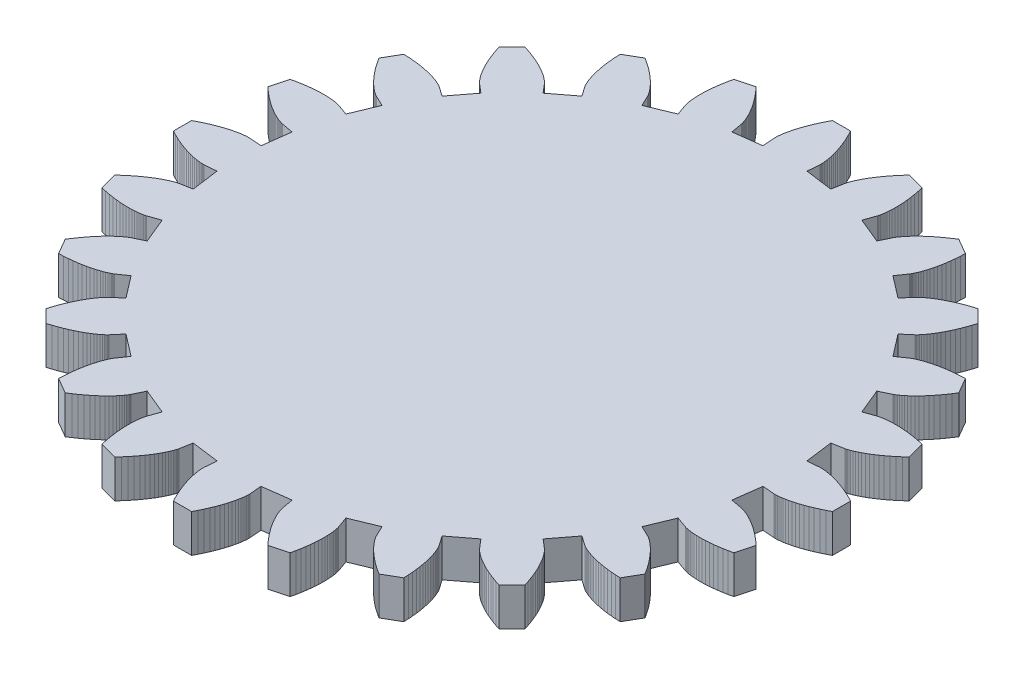
SolidWorks part; units mm, degrees
ref_plane "Front Plane" through (0, 0, 0) normal (0, 0, 1) x (1, 0, 0)
ref_plane "Top Plane" through (0, 0, 0) normal (0, 1, 0) x (1, 0, 0)
ref_plane "Right Plane" through (0, 0, 0) normal (1, 0, 0) x (0, 0, -1)
sketch "Sketch1" plane through (0, 0, 0) normal (0, 1, 0) x (1, 0, 0)
  line L0 (21.5303, 1.7338) -> (22.4799, 1.8102)
  line L1 (22.4799, 1.8102) -> (22.4901, 1.8109)
  line L2 (22.4901, 1.8109) -> (22.5209, 1.8119)
  line L3 (22.5209, 1.8119) -> (22.5723, 1.8121)
  line L4 (22.5723, 1.8121) -> (22.6443, 1.8102)
  line L5 (22.6443, 1.8102) -> (22.7366, 1.805)
  line L6 (22.7366, 1.805) -> (22.8493, 1.7953)
  line L7 (22.8493, 1.7953) -> (22.982, 1.7798)
  line L8 (22.982, 1.7798) -> (23.1345, 1.7573)
  line L9 (23.1345, 1.7573) -> (23.3066, 1.7266)
  line L10 (23.3066, 1.7266) -> (23.4977, 1.6865)
  line L11 (23.4977, 1.6865) -> (23.7075, 1.6359)
  line L12 (23.7075, 1.6359) -> (23.9356, 1.5735)
  line L13 (23.9356, 1.5735) -> (24.1813, 1.4982)
  line L14 (24.1813, 1.4982) -> (24.4441, 1.4089)
  line L15 (24.4441, 1.4089) -> (24.7233, 1.3046)
  line L16 (24.7233, 1.3046) -> (25.0183, 1.1841)
  line L17 (25.0183, 1.1841) -> (25.3283, 1.0464)
  line L18 (25.3283, 1.0464) -> (25.6525, 0.8905)
  line L19 (25.6525, 0.8905) -> (25.9901, 0.7155)
  line L20 (25.9901, 0.7155) -> (25.9901, -0.7155)
  line L21 (25.9901, -0.7155) -> (25.6525, -0.8905)
  line L22 (25.6525, -0.8905) -> (25.3283, -1.0464)
  line L23 (25.3283, -1.0464) -> (25.0183, -1.1841)
  line L24 (25.0183, -1.1841) -> (24.7233, -1.3046)
  line L25 (24.7233, -1.3046) -> (24.4441, -1.4089)
  line L26 (24.4441, -1.4089) -> (24.1813, -1.4982)
  line L27 (24.1813, -1.4982) -> (23.9356, -1.5735)
  line L28 (23.9356, -1.5735) -> (23.7075, -1.6359)
  line L29 (23.7075, -1.6359) -> (23.4977, -1.6865)
  line L30 (23.4977, -1.6865) -> (23.3066, -1.7266)
  line L31 (23.3066, -1.7266) -> (23.1345, -1.7573)
  line L32 (23.1345, -1.7573) -> (22.982, -1.7798)
  line L33 (22.982, -1.7798) -> (22.8493, -1.7953)
  line L34 (22.8493, -1.7953) -> (22.7366, -1.805)
  line L35 (22.7366, -1.805) -> (22.6443, -1.8102)
  line L36 (22.6443, -1.8102) -> (22.5723, -1.8121)
  line L37 (22.5723, -1.8121) -> (22.5209, -1.8119)
  line L38 (22.5209, -1.8119) -> (22.4901, -1.8109)
  line L39 (22.4901, -1.8109) -> (22.4799, -1.8102)
  line L40 (22.4799, -1.8102) -> (21.5303, -1.7338)
  line L41 (21.5303, -1.7338) -> (21.2454, -3.8977)
  line L42 (21.2454, -3.8977) -> (22.1824, -4.0696)
  line L43 (22.1824, -4.0696) -> (22.1925, -4.0717)
  line L44 (22.1925, -4.0717) -> (22.2225, -4.0787)
  line L45 (22.2225, -4.0787) -> (22.2722, -4.0918)
  line L46 (22.2722, -4.0918) -> (22.3412, -4.1122)
  line L47 (22.3412, -4.1122) -> (22.4291, -4.1411)
  line L48 (22.4291, -4.1411) -> (22.5354, -4.1797)
  line L49 (22.5354, -4.1797) -> (22.6595, -4.229)
  line L50 (22.6595, -4.229) -> (22.8011, -4.2902)
  line L51 (22.8011, -4.2902) -> (22.9593, -4.3644)
  line L52 (22.9593, -4.3644) -> (23.1335, -4.4526)
  line L53 (23.1335, -4.4526) -> (23.3231, -4.5558)
  line L54 (23.3231, -4.5558) -> (23.5272, -4.6751)
  line L55 (23.5272, -4.6751) -> (23.7451, -4.8114)
  line L56 (23.7451, -4.8114) -> (23.9758, -4.9657)
  line L57 (23.9758, -4.9657) -> (24.2185, -5.1387)
  line L58 (24.2185, -5.1387) -> (24.4723, -5.3314)
  line L59 (24.4723, -5.3314) -> (24.7361, -5.5447)
  line L60 (24.7361, -5.5447) -> (25.0089, -5.7792)
  line L61 (25.0089, -5.7792) -> (25.2897, -6.0357)
  line L62 (25.2897, -6.0357) -> (24.9194, -7.4178)
  line L63 (24.9194, -7.4178) -> (24.5479, -7.4995)
  line L64 (24.5479, -7.4995) -> (24.1944, -7.5662)
  line L65 (24.1944, -7.5662) -> (23.8593, -7.619)
  line L66 (23.8593, -7.619) -> (23.5432, -7.659)
  line L67 (23.5432, -7.659) -> (23.2465, -7.6875)
  line L68 (23.2465, -7.6875) -> (22.9695, -7.7057)
  line L69 (22.9695, -7.7057) -> (22.7127, -7.7148)
  line L70 (22.7127, -7.7148) -> (22.4763, -7.7161)
  line L71 (22.4763, -7.7161) -> (22.2605, -7.7107)
  line L72 (22.2605, -7.7107) -> (22.0655, -7.7)
  line L73 (22.0655, -7.7) -> (21.8914, -7.6851)
  line L74 (21.8914, -7.6851) -> (21.7383, -7.6673)
  line L75 (21.7383, -7.6673) -> (21.606, -7.648)
  line L76 (21.606, -7.648) -> (21.4947, -7.6282)
  line L77 (21.4947, -7.6282) -> (21.4042, -7.6093)
  line L78 (21.4042, -7.6093) -> (21.3342, -7.5925)
  line L79 (21.3342, -7.5925) -> (21.2846, -7.579)
  line L80 (21.2846, -7.579) -> (21.2551, -7.57)
  line L81 (21.2551, -7.57) -> (21.2453, -7.5668)
  line L82 (21.2453, -7.5668) -> (20.3479, -7.2472)
  line L83 (20.3479, -7.2472) -> (19.5127, -9.2637)
  line L84 (19.5127, -9.2637) -> (20.3732, -9.6722)
  line L85 (20.3732, -9.6722) -> (20.3824, -9.6768)
  line L86 (20.3824, -9.6768) -> (20.4096, -9.6913)
  line L87 (20.4096, -9.6913) -> (20.4543, -9.7168)
  line L88 (20.4543, -9.7168) -> (20.5156, -9.7544)
  line L89 (20.5156, -9.7544) -> (20.593, -9.8051)
  line L90 (20.593, -9.8051) -> (20.6857, -9.8699)
  line L91 (20.6857, -9.8699) -> (20.7929, -9.9496)
  line L92 (20.7929, -9.9496) -> (20.9137, -10.0454)
  line L93 (20.9137, -10.0454) -> (21.0474, -10.158)
  line L94 (21.0474, -10.158) -> (21.1929, -10.2883)
  line L95 (21.1929, -10.2883) -> (21.3492, -10.4371)
  line L96 (21.3492, -10.4371) -> (21.5155, -10.6051)
  line L97 (21.5155, -10.6051) -> (21.6907, -10.7932)
  line L98 (21.6907, -10.7932) -> (21.8736, -11.0018)
  line L99 (21.8736, -11.0018) -> (22.0633, -11.2318)
  line L100 (22.0633, -11.2318) -> (22.2585, -11.4837)
  line L101 (22.2585, -11.4837) -> (22.4581, -11.7579)
  line L102 (22.4581, -11.7579) -> (22.661, -12.055)
  line L103 (22.661, -12.055) -> (22.8659, -12.3755)
  line L104 (22.8659, -12.3755) -> (22.1504, -13.6147)
  line L105 (22.1504, -13.6147) -> (21.7705, -13.5975)
  line L106 (21.7705, -13.5975) -> (21.4117, -13.5704)
  line L107 (21.4117, -13.5704) -> (21.0744, -13.5346)
  line L108 (21.0744, -13.5346) -> (20.7587, -13.4915)
  line L109 (20.7587, -13.4915) -> (20.4647, -13.4422)
  line L110 (20.4647, -13.4422) -> (20.1925, -13.3881)
  line L111 (20.1925, -13.3881) -> (19.9421, -13.3304)
  line L112 (19.9421, -13.3304) -> (19.7134, -13.2705)
  line L113 (19.7134, -13.2705) -> (19.5063, -13.2094)
  line L114 (19.5063, -13.2094) -> (19.3208, -13.1486)
  line L115 (19.3208, -13.1486) -> (19.1564, -13.0891)
  line L116 (19.1564, -13.0891) -> (19.0131, -13.0324)
  line L117 (19.0131, -13.0324) -> (18.8904, -12.9794)
  line L118 (18.8904, -12.9794) -> (18.788, -12.9315)
  line L119 (18.788, -12.9315) -> (18.7054, -12.8898)
  line L120 (18.7054, -12.8898) -> (18.6422, -12.8555)
  line L121 (18.6422, -12.8555) -> (18.5978, -12.8296)
  line L122 (18.5978, -12.8296) -> (18.5716, -12.8133)
  line L123 (18.5716, -12.8133) -> (18.563, -12.8076)
  line L124 (18.563, -12.8076) -> (17.7789, -12.2667)
  line L125 (17.7789, -12.2667) -> (16.4502, -13.9983)
  line L126 (16.4502, -13.9983) -> (17.1757, -14.6156)
  line L127 (17.1757, -14.6156) -> (17.1834, -14.6224)
  line L128 (17.1834, -14.6224) -> (17.2059, -14.6435)
  line L129 (17.2059, -14.6435) -> (17.2424, -14.6797)
  line L130 (17.2424, -14.6797) -> (17.2919, -14.7319)
  line L131 (17.2919, -14.7319) -> (17.3536, -14.8009)
  line L132 (17.3536, -14.8009) -> (17.4263, -14.8874)
  line L133 (17.4263, -14.8874) -> (17.5092, -14.9922)
  line L134 (17.5092, -14.9922) -> (17.6012, -15.116)
  line L135 (17.6012, -15.116) -> (17.7011, -15.2593)
  line L136 (17.7011, -15.2593) -> (17.8079, -15.4228)
  line L137 (17.8079, -15.4228) -> (17.9205, -15.607)
  line L138 (17.9205, -15.607) -> (18.0376, -15.8124)
  line L139 (18.0376, -15.8124) -> (18.1581, -16.0393)
  line L140 (18.1581, -16.0393) -> (18.2808, -16.2883)
  line L141 (18.2808, -16.2883) -> (18.4045, -16.5595)
  line L142 (18.4045, -16.5595) -> (18.5279, -16.8533)
  line L143 (18.5279, -16.8533) -> (18.6497, -17.1699)
  line L144 (18.6497, -17.1699) -> (18.7688, -17.5094)
  line L145 (18.7688, -17.5094) -> (18.8837, -17.8719)
  line L146 (18.8837, -17.8719) -> (17.8719, -18.8837)
  line L147 (17.8719, -18.8837) -> (17.5094, -18.7688)
  line L148 (17.5094, -18.7688) -> (17.1699, -18.6497)
  line L149 (17.1699, -18.6497) -> (16.8533, -18.5279)
  line L150 (16.8533, -18.5279) -> (16.5595, -18.4045)
  line L151 (16.5595, -18.4045) -> (16.2883, -18.2808)
  line L152 (16.2883, -18.2808) -> (16.0393, -18.1581)
  line L153 (16.0393, -18.1581) -> (15.8124, -18.0376)
  line L154 (15.8124, -18.0376) -> (15.607, -17.9205)
  line L155 (15.607, -17.9205) -> (15.4228, -17.8079)
  line L156 (15.4228, -17.8079) -> (15.2593, -17.7011)
  line L157 (15.2593, -17.7011) -> (15.116, -17.6012)
  line L158 (15.116, -17.6012) -> (14.9922, -17.5092)
  line L159 (14.9922, -17.5092) -> (14.8874, -17.4263)
  line L160 (14.8874, -17.4263) -> (14.8009, -17.3536)
  line L161 (14.8009, -17.3536) -> (14.7319, -17.2919)
  line L162 (14.7319, -17.2919) -> (14.6797, -17.2424)
  line L163 (14.6797, -17.2424) -> (14.6435, -17.2059)
  line L164 (14.6435, -17.2059) -> (14.6224, -17.1834)
  line L165 (14.6224, -17.1834) -> (14.6156, -17.1757)
  line L166 (14.6156, -17.1757) -> (13.9983, -16.4502)
  line L167 (13.9983, -16.4502) -> (12.2667, -17.7789)
  line L168 (12.2667, -17.7789) -> (12.8076, -18.563)
  line L169 (12.8076, -18.563) -> (12.8133, -18.5716)
  line L170 (12.8133, -18.5716) -> (12.8296, -18.5978)
  line L171 (12.8296, -18.5978) -> (12.8555, -18.6422)
  line L172 (12.8555, -18.6422) -> (12.8898, -18.7054)
  line L173 (12.8898, -18.7054) -> (12.9315, -18.788)
  line L174 (12.9315, -18.788) -> (12.9794, -18.8904)
  line L175 (12.9794, -18.8904) -> (13.0324, -19.0131)
  line L176 (13.0324, -19.0131) -> (13.0891, -19.1564)
  line L177 (13.0891, -19.1564) -> (13.1486, -19.3208)
  line L178 (13.1486, -19.3208) -> (13.2094, -19.5063)
  line L179 (13.2094, -19.5063) -> (13.2705, -19.7134)
  line L180 (13.2705, -19.7134) -> (13.3304, -19.9421)
  line L181 (13.3304, -19.9421) -> (13.3881, -20.1925)
  line L182 (13.3881, -20.1925) -> (13.4422, -20.4647)
  line L183 (13.4422, -20.4647) -> (13.4915, -20.7587)
  line L184 (13.4915, -20.7587) -> (13.5346, -21.0744)
  line L185 (13.5346, -21.0744) -> (13.5704, -21.4117)
  line L186 (13.5704, -21.4117) -> (13.5975, -21.7705)
  line L187 (13.5975, -21.7705) -> (13.6147, -22.1504)
  line L188 (13.6147, -22.1504) -> (12.3755, -22.8659)
  line L189 (12.3755, -22.8659) -> (12.055, -22.661)
  line L190 (12.055, -22.661) -> (11.7579, -22.4581)
  line L191 (11.7579, -22.4581) -> (11.4837, -22.2585)
  line L192 (11.4837, -22.2585) -> (11.2318, -22.0633)
  line L193 (11.2318, -22.0633) -> (11.0018, -21.8736)
  line L194 (11.0018, -21.8736) -> (10.7932, -21.6907)
  line L195 (10.7932, -21.6907) -> (10.6051, -21.5155)
  line L196 (10.6051, -21.5155) -> (10.4371, -21.3492)
  line L197 (10.4371, -21.3492) -> (10.2883, -21.1929)
  line L198 (10.2883, -21.1929) -> (10.158, -21.0474)
  line L199 (10.158, -21.0474) -> (10.0454, -20.9137)
  line L200 (10.0454, -20.9137) -> (9.9496, -20.7929)
  line L201 (9.9496, -20.7929) -> (9.8699, -20.6857)
  line L202 (9.8699, -20.6857) -> (9.8051, -20.593)
  line L203 (9.8051, -20.593) -> (9.7544, -20.5156)
  line L204 (9.7544, -20.5156) -> (9.7168, -20.4543)
  line L205 (9.7168, -20.4543) -> (9.6913, -20.4096)
  line L206 (9.6913, -20.4096) -> (9.6768, -20.3824)
  line L207 (9.6768, -20.3824) -> (9.6722, -20.3732)
  line L208 (9.6722, -20.3732) -> (9.2637, -19.5127)
  line L209 (9.2637, -19.5127) -> (7.2472, -20.3479)
  line L210 (7.2472, -20.3479) -> (7.5668, -21.2453)
  line L211 (7.5668, -21.2453) -> (7.57, -21.2551)
  line L212 (7.57, -21.2551) -> (7.579, -21.2846)
  line L213 (7.579, -21.2846) -> (7.5925, -21.3342)
  line L214 (7.5925, -21.3342) -> (7.6093, -21.4042)
  line L215 (7.6093, -21.4042) -> (7.6282, -21.4947)
  line L216 (7.6282, -21.4947) -> (7.648, -21.606)
  line L217 (7.648, -21.606) -> (7.6673, -21.7383)
  line L218 (7.6673, -21.7383) -> (7.6851, -21.8914)
  line L219 (7.6851, -21.8914) -> (7.7, -22.0655)
  line L220 (7.7, -22.0655) -> (7.7107, -22.2605)
  line L221 (7.7107, -22.2605) -> (7.7161, -22.4763)
  line L222 (7.7161, -22.4763) -> (7.7148, -22.7127)
  line L223 (7.7148, -22.7127) -> (7.7057, -22.9695)
  line L224 (7.7057, -22.9695) -> (7.6875, -23.2465)
  line L225 (7.6875, -23.2465) -> (7.659, -23.5432)
  line L226 (7.659, -23.5432) -> (7.619, -23.8593)
  line L227 (7.619, -23.8593) -> (7.5662, -24.1944)
  line L228 (7.5662, -24.1944) -> (7.4995, -24.5479)
  line L229 (7.4995, -24.5479) -> (7.4178, -24.9194)
  line L230 (7.4178, -24.9194) -> (6.0357, -25.2897)
  line L231 (6.0357, -25.2897) -> (5.7792, -25.0089)
  line L232 (5.7792, -25.0089) -> (5.5447, -24.7361)
  line L233 (5.5447, -24.7361) -> (5.3314, -24.4723)
  line L234 (5.3314, -24.4723) -> (5.1387, -24.2185)
  line L235 (5.1387, -24.2185) -> (4.9657, -23.9758)
  line L236 (4.9657, -23.9758) -> (4.8114, -23.7451)
  line L237 (4.8114, -23.7451) -> (4.6751, -23.5272)
  line L238 (4.6751, -23.5272) -> (4.5558, -23.3231)
  line L239 (4.5558, -23.3231) -> (4.4526, -23.1335)
  line L240 (4.4526, -23.1335) -> (4.3644, -22.9593)
  line L241 (4.3644, -22.9593) -> (4.2902, -22.8011)
  line L242 (4.2902, -22.8011) -> (4.229, -22.6595)
  line L243 (4.229, -22.6595) -> (4.1797, -22.5354)
  line L244 (4.1797, -22.5354) -> (4.1411, -22.4291)
  line L245 (4.1411, -22.4291) -> (4.1122, -22.3412)
  line L246 (4.1122, -22.3412) -> (4.0918, -22.2722)
  line L247 (4.0918, -22.2722) -> (4.0787, -22.2225)
  line L248 (4.0787, -22.2225) -> (4.0717, -22.1925)
  line L249 (4.0717, -22.1925) -> (4.0696, -22.1824)
  line L250 (4.0696, -22.1824) -> (3.8977, -21.2454)
  line L251 (3.8977, -21.2454) -> (1.7338, -21.5303)
  line L252 (1.7338, -21.5303) -> (1.8102, -22.4799)
  line L253 (1.8102, -22.4799) -> (1.8109, -22.4901)
  line L254 (1.8109, -22.4901) -> (1.8119, -22.5209)
  line L255 (1.8119, -22.5209) -> (1.8121, -22.5723)
  line L256 (1.8121, -22.5723) -> (1.8102, -22.6443)
  line L257 (1.8102, -22.6443) -> (1.805, -22.7366)
  line L258 (1.805, -22.7366) -> (1.7953, -22.8493)
  line L259 (1.7953, -22.8493) -> (1.7798, -22.982)
  line L260 (1.7798, -22.982) -> (1.7573, -23.1345)
  line L261 (1.7573, -23.1345) -> (1.7266, -23.3066)
  line L262 (1.7266, -23.3066) -> (1.6865, -23.4977)
  line L263 (1.6865, -23.4977) -> (1.6359, -23.7075)
  line L264 (1.6359, -23.7075) -> (1.5735, -23.9356)
  line L265 (1.5735, -23.9356) -> (1.4982, -24.1813)
  line L266 (1.4982, -24.1813) -> (1.4089, -24.4441)
  line L267 (1.4089, -24.4441) -> (1.3046, -24.7233)
  line L268 (1.3046, -24.7233) -> (1.1841, -25.0183)
  line L269 (1.1841, -25.0183) -> (1.0464, -25.3283)
  line L270 (1.0464, -25.3283) -> (0.8905, -25.6525)
  line L271 (0.8905, -25.6525) -> (0.7155, -25.9901)
  line L272 (0.7155, -25.9901) -> (-0.7155, -25.9901)
  line L273 (-0.7155, -25.9901) -> (-0.8905, -25.6525)
  line L274 (-0.8905, -25.6525) -> (-1.0464, -25.3283)
  line L275 (-1.0464, -25.3283) -> (-1.1841, -25.0183)
  line L276 (-1.1841, -25.0183) -> (-1.3046, -24.7233)
  line L277 (-1.3046, -24.7233) -> (-1.4089, -24.4441)
  line L278 (-1.4089, -24.4441) -> (-1.4982, -24.1813)
  line L279 (-1.4982, -24.1813) -> (-1.5735, -23.9356)
  line L280 (-1.5735, -23.9356) -> (-1.6359, -23.7075)
  line L281 (-1.6359, -23.7075) -> (-1.6865, -23.4977)
  line L282 (-1.6865, -23.4977) -> (-1.7266, -23.3066)
  line L283 (-1.7266, -23.3066) -> (-1.7573, -23.1345)
  line L284 (-1.7573, -23.1345) -> (-1.7798, -22.982)
  line L285 (-1.7798, -22.982) -> (-1.7953, -22.8493)
  line L286 (-1.7953, -22.8493) -> (-1.805, -22.7366)
  line L287 (-1.805, -22.7366) -> (-1.8102, -22.6443)
  line L288 (-1.8102, -22.6443) -> (-1.8121, -22.5723)
  line L289 (-1.8121, -22.5723) -> (-1.8119, -22.5209)
  line L290 (-1.8119, -22.5209) -> (-1.8109, -22.4901)
  line L291 (-1.8109, -22.4901) -> (-1.8102, -22.4799)
  line L292 (-1.8102, -22.4799) -> (-1.7338, -21.5303)
  line L293 (-1.7338, -21.5303) -> (-3.8977, -21.2454)
  line L294 (-3.8977, -21.2454) -> (-4.0696, -22.1824)
  line L295 (-4.0696, -22.1824) -> (-4.0717, -22.1925)
  line L296 (-4.0717, -22.1925) -> (-4.0787, -22.2225)
  line L297 (-4.0787, -22.2225) -> (-4.0918, -22.2722)
  line L298 (-4.0918, -22.2722) -> (-4.1122, -22.3412)
  line L299 (-4.1122, -22.3412) -> (-4.1411, -22.4291)
  line L300 (-4.1411, -22.4291) -> (-4.1797, -22.5354)
  line L301 (-4.1797, -22.5354) -> (-4.229, -22.6595)
  line L302 (-4.229, -22.6595) -> (-4.2902, -22.8011)
  line L303 (-4.2902, -22.8011) -> (-4.3644, -22.9593)
  line L304 (-4.3644, -22.9593) -> (-4.4526, -23.1335)
  line L305 (-4.4526, -23.1335) -> (-4.5558, -23.3231)
  line L306 (-4.5558, -23.3231) -> (-4.6751, -23.5272)
  line L307 (-4.6751, -23.5272) -> (-4.8114, -23.7451)
  line L308 (-4.8114, -23.7451) -> (-4.9657, -23.9758)
  line L309 (-4.9657, -23.9758) -> (-5.1387, -24.2185)
  line L310 (-5.1387, -24.2185) -> (-5.3314, -24.4723)
  line L311 (-5.3314, -24.4723) -> (-5.5447, -24.7361)
  line L312 (-5.5447, -24.7361) -> (-5.7792, -25.0089)
  line L313 (-5.7792, -25.0089) -> (-6.0357, -25.2897)
  line L314 (-6.0357, -25.2897) -> (-7.4178, -24.9194)
  line L315 (-7.4178, -24.9194) -> (-7.4995, -24.5479)
  line L316 (-7.4995, -24.5479) -> (-7.5662, -24.1944)
  line L317 (-7.5662, -24.1944) -> (-7.619, -23.8593)
  line L318 (-7.619, -23.8593) -> (-7.659, -23.5432)
  line L319 (-7.659, -23.5432) -> (-7.6875, -23.2465)
  line L320 (-7.6875, -23.2465) -> (-7.7057, -22.9695)
  line L321 (-7.7057, -22.9695) -> (-7.7148, -22.7127)
  line L322 (-7.7148, -22.7127) -> (-7.7161, -22.4763)
  line L323 (-7.7161, -22.4763) -> (-7.7107, -22.2605)
  line L324 (-7.7107, -22.2605) -> (-7.7, -22.0655)
  line L325 (-7.7, -22.0655) -> (-7.6851, -21.8914)
  line L326 (-7.6851, -21.8914) -> (-7.6673, -21.7383)
  line L327 (-7.6673, -21.7383) -> (-7.648, -21.606)
  line L328 (-7.648, -21.606) -> (-7.6282, -21.4947)
  line L329 (-7.6282, -21.4947) -> (-7.6093, -21.4042)
  line L330 (-7.6093, -21.4042) -> (-7.5925, -21.3342)
  line L331 (-7.5925, -21.3342) -> (-7.579, -21.2846)
  line L332 (-7.579, -21.2846) -> (-7.57, -21.2551)
  line L333 (-7.57, -21.2551) -> (-7.5668, -21.2453)
  line L334 (-7.5668, -21.2453) -> (-7.2472, -20.3479)
  line L335 (-7.2472, -20.3479) -> (-9.2637, -19.5127)
  line L336 (-9.2637, -19.5127) -> (-9.6722, -20.3732)
  line L337 (-9.6722, -20.3732) -> (-9.6768, -20.3824)
  line L338 (-9.6768, -20.3824) -> (-9.6913, -20.4096)
  line L339 (-9.6913, -20.4096) -> (-9.7168, -20.4543)
  line L340 (-9.7168, -20.4543) -> (-9.7544, -20.5156)
  line L341 (-9.7544, -20.5156) -> (-9.8051, -20.593)
  line L342 (-9.8051, -20.593) -> (-9.8699, -20.6857)
  line L343 (-9.8699, -20.6857) -> (-9.9496, -20.7929)
  line L344 (-9.9496, -20.7929) -> (-10.0454, -20.9137)
  line L345 (-10.0454, -20.9137) -> (-10.158, -21.0474)
  line L346 (-10.158, -21.0474) -> (-10.2883, -21.1929)
  line L347 (-10.2883, -21.1929) -> (-10.4371, -21.3492)
  line L348 (-10.4371, -21.3492) -> (-10.6051, -21.5155)
  line L349 (-10.6051, -21.5155) -> (-10.7932, -21.6907)
  line L350 (-10.7932, -21.6907) -> (-11.0018, -21.8736)
  line L351 (-11.0018, -21.8736) -> (-11.2318, -22.0633)
  line L352 (-11.2318, -22.0633) -> (-11.4837, -22.2585)
  line L353 (-11.4837, -22.2585) -> (-11.7579, -22.4581)
  line L354 (-11.7579, -22.4581) -> (-12.055, -22.661)
  line L355 (-12.055, -22.661) -> (-12.3755, -22.8659)
  line L356 (-12.3755, -22.8659) -> (-13.6147, -22.1504)
  line L357 (-13.6147, -22.1504) -> (-13.5975, -21.7705)
  line L358 (-13.5975, -21.7705) -> (-13.5704, -21.4117)
  line L359 (-13.5704, -21.4117) -> (-13.5346, -21.0744)
  line L360 (-13.5346, -21.0744) -> (-13.4915, -20.7587)
  line L361 (-13.4915, -20.7587) -> (-13.4422, -20.4647)
  line L362 (-13.4422, -20.4647) -> (-13.3881, -20.1925)
  line L363 (-13.3881, -20.1925) -> (-13.3304, -19.9421)
  line L364 (-13.3304, -19.9421) -> (-13.2705, -19.7134)
  line L365 (-13.2705, -19.7134) -> (-13.2094, -19.5063)
  line L366 (-13.2094, -19.5063) -> (-13.1486, -19.3208)
  line L367 (-13.1486, -19.3208) -> (-13.0891, -19.1564)
  line L368 (-13.0891, -19.1564) -> (-13.0324, -19.0131)
  line L369 (-13.0324, -19.0131) -> (-12.9794, -18.8904)
  line L370 (-12.9794, -18.8904) -> (-12.9315, -18.788)
  line L371 (-12.9315, -18.788) -> (-12.8898, -18.7054)
  line L372 (-12.8898, -18.7054) -> (-12.8555, -18.6422)
  line L373 (-12.8555, -18.6422) -> (-12.8296, -18.5978)
  line L374 (-12.8296, -18.5978) -> (-12.8133, -18.5716)
  line L375 (-12.8133, -18.5716) -> (-12.8076, -18.563)
  line L376 (-12.8076, -18.563) -> (-12.2667, -17.7789)
  line L377 (-12.2667, -17.7789) -> (-13.9983, -16.4502)
  line L378 (-13.9983, -16.4502) -> (-14.6156, -17.1757)
  line L379 (-14.6156, -17.1757) -> (-14.6224, -17.1834)
  line L380 (-14.6224, -17.1834) -> (-14.6435, -17.2059)
  line L381 (-14.6435, -17.2059) -> (-14.6797, -17.2424)
  line L382 (-14.6797, -17.2424) -> (-14.7319, -17.2919)
  line L383 (-14.7319, -17.2919) -> (-14.8009, -17.3536)
  line L384 (-14.8009, -17.3536) -> (-14.8874, -17.4263)
  line L385 (-14.8874, -17.4263) -> (-14.9922, -17.5092)
  line L386 (-14.9922, -17.5092) -> (-15.116, -17.6012)
  line L387 (-15.116, -17.6012) -> (-15.2593, -17.7011)
  line L388 (-15.2593, -17.7011) -> (-15.4228, -17.8079)
  line L389 (-15.4228, -17.8079) -> (-15.607, -17.9205)
  line L390 (-15.607, -17.9205) -> (-15.8124, -18.0376)
  line L391 (-15.8124, -18.0376) -> (-16.0393, -18.1581)
  line L392 (-16.0393, -18.1581) -> (-16.2883, -18.2808)
  line L393 (-16.2883, -18.2808) -> (-16.5595, -18.4045)
  line L394 (-16.5595, -18.4045) -> (-16.8533, -18.5279)
  line L395 (-16.8533, -18.5279) -> (-17.1699, -18.6497)
  line L396 (-17.1699, -18.6497) -> (-17.5094, -18.7688)
  line L397 (-17.5094, -18.7688) -> (-17.8719, -18.8837)
  line L398 (-17.8719, -18.8837) -> (-18.8837, -17.8719)
  line L399 (-18.8837, -17.8719) -> (-18.7688, -17.5094)
  line L400 (-18.7688, -17.5094) -> (-18.6497, -17.1699)
  line L401 (-18.6497, -17.1699) -> (-18.5279, -16.8533)
  line L402 (-18.5279, -16.8533) -> (-18.4045, -16.5595)
  line L403 (-18.4045, -16.5595) -> (-18.2808, -16.2883)
  line L404 (-18.2808, -16.2883) -> (-18.1581, -16.0393)
  line L405 (-18.1581, -16.0393) -> (-18.0376, -15.8124)
  line L406 (-18.0376, -15.8124) -> (-17.9205, -15.607)
  line L407 (-17.9205, -15.607) -> (-17.8079, -15.4228)
  line L408 (-17.8079, -15.4228) -> (-17.7011, -15.2593)
  line L409 (-17.7011, -15.2593) -> (-17.6012, -15.116)
  line L410 (-17.6012, -15.116) -> (-17.5092, -14.9922)
  line L411 (-17.5092, -14.9922) -> (-17.4263, -14.8874)
  line L412 (-17.4263, -14.8874) -> (-17.3536, -14.8009)
  line L413 (-17.3536, -14.8009) -> (-17.2919, -14.7319)
  line L414 (-17.2919, -14.7319) -> (-17.2424, -14.6797)
  line L415 (-17.2424, -14.6797) -> (-17.2059, -14.6435)
  line L416 (-17.2059, -14.6435) -> (-17.1834, -14.6224)
  line L417 (-17.1834, -14.6224) -> (-17.1757, -14.6156)
  line L418 (-17.1757, -14.6156) -> (-16.4502, -13.9983)
  line L419 (-16.4502, -13.9983) -> (-17.7789, -12.2667)
  line L420 (-17.7789, -12.2667) -> (-18.563, -12.8076)
  line L421 (-18.563, -12.8076) -> (-18.5716, -12.8133)
  line L422 (-18.5716, -12.8133) -> (-18.5978, -12.8296)
  line L423 (-18.5978, -12.8296) -> (-18.6422, -12.8555)
  line L424 (-18.6422, -12.8555) -> (-18.7054, -12.8898)
  line L425 (-18.7054, -12.8898) -> (-18.788, -12.9315)
  line L426 (-18.788, -12.9315) -> (-18.8904, -12.9794)
  line L427 (-18.8904, -12.9794) -> (-19.0131, -13.0324)
  line L428 (-19.0131, -13.0324) -> (-19.1564, -13.0891)
  line L429 (-19.1564, -13.0891) -> (-19.3208, -13.1486)
  line L430 (-19.3208, -13.1486) -> (-19.5063, -13.2094)
  line L431 (-19.5063, -13.2094) -> (-19.7134, -13.2705)
  line L432 (-19.7134, -13.2705) -> (-19.9421, -13.3304)
  line L433 (-19.9421, -13.3304) -> (-20.1925, -13.3881)
  line L434 (-20.1925, -13.3881) -> (-20.4647, -13.4422)
  line L435 (-20.4647, -13.4422) -> (-20.7587, -13.4915)
  line L436 (-20.7587, -13.4915) -> (-21.0744, -13.5346)
  line L437 (-21.0744, -13.5346) -> (-21.4117, -13.5704)
  line L438 (-21.4117, -13.5704) -> (-21.7705, -13.5975)
  line L439 (-21.7705, -13.5975) -> (-22.1504, -13.6147)
  line L440 (-22.1504, -13.6147) -> (-22.8659, -12.3755)
  line L441 (-22.8659, -12.3755) -> (-22.661, -12.055)
  line L442 (-22.661, -12.055) -> (-22.4581, -11.7579)
  line L443 (-22.4581, -11.7579) -> (-22.2585, -11.4837)
  line L444 (-22.2585, -11.4837) -> (-22.0633, -11.2318)
  line L445 (-22.0633, -11.2318) -> (-21.8736, -11.0018)
  line L446 (-21.8736, -11.0018) -> (-21.6907, -10.7932)
  line L447 (-21.6907, -10.7932) -> (-21.5155, -10.6051)
  line L448 (-21.5155, -10.6051) -> (-21.3492, -10.4371)
  line L449 (-21.3492, -10.4371) -> (-21.1929, -10.2883)
  line L450 (-21.1929, -10.2883) -> (-21.0474, -10.158)
  line L451 (-21.0474, -10.158) -> (-20.9137, -10.0454)
  line L452 (-20.9137, -10.0454) -> (-20.7929, -9.9496)
  line L453 (-20.7929, -9.9496) -> (-20.6857, -9.8699)
  line L454 (-20.6857, -9.8699) -> (-20.593, -9.8051)
  line L455 (-20.593, -9.8051) -> (-20.5156, -9.7544)
  line L456 (-20.5156, -9.7544) -> (-20.4543, -9.7168)
  line L457 (-20.4543, -9.7168) -> (-20.4096, -9.6913)
  line L458 (-20.4096, -9.6913) -> (-20.3824, -9.6768)
  line L459 (-20.3824, -9.6768) -> (-20.3732, -9.6722)
  line L460 (-20.3732, -9.6722) -> (-19.5127, -9.2637)
  line L461 (-19.5127, -9.2637) -> (-20.3479, -7.2472)
  line L462 (-20.3479, -7.2472) -> (-21.2453, -7.5668)
  line L463 (-21.2453, -7.5668) -> (-21.2551, -7.57)
  line L464 (-21.2551, -7.57) -> (-21.2846, -7.579)
  line L465 (-21.2846, -7.579) -> (-21.3342, -7.5925)
  line L466 (-21.3342, -7.5925) -> (-21.4042, -7.6093)
  line L467 (-21.4042, -7.6093) -> (-21.4947, -7.6282)
  line L468 (-21.4947, -7.6282) -> (-21.606, -7.648)
  line L469 (-21.606, -7.648) -> (-21.7383, -7.6673)
  line L470 (-21.7383, -7.6673) -> (-21.8914, -7.6851)
  line L471 (-21.8914, -7.6851) -> (-22.0655, -7.7)
  line L472 (-22.0655, -7.7) -> (-22.2605, -7.7107)
  line L473 (-22.2605, -7.7107) -> (-22.4763, -7.7161)
  line L474 (-22.4763, -7.7161) -> (-22.7127, -7.7148)
  line L475 (-22.7127, -7.7148) -> (-22.9695, -7.7057)
  line L476 (-22.9695, -7.7057) -> (-23.2465, -7.6875)
  line L477 (-23.2465, -7.6875) -> (-23.5432, -7.659)
  line L478 (-23.5432, -7.659) -> (-23.8593, -7.619)
  line L479 (-23.8593, -7.619) -> (-24.1944, -7.5662)
  line L480 (-24.1944, -7.5662) -> (-24.5479, -7.4995)
  line L481 (-24.5479, -7.4995) -> (-24.9194, -7.4178)
  line L482 (-24.9194, -7.4178) -> (-25.2897, -6.0357)
  line L483 (-25.2897, -6.0357) -> (-25.0089, -5.7792)
  line L484 (-25.0089, -5.7792) -> (-24.7361, -5.5447)
  line L485 (-24.7361, -5.5447) -> (-24.4723, -5.3314)
  line L486 (-24.4723, -5.3314) -> (-24.2185, -5.1387)
  line L487 (-24.2185, -5.1387) -> (-23.9758, -4.9657)
  line L488 (-23.9758, -4.9657) -> (-23.7451, -4.8114)
  line L489 (-23.7451, -4.8114) -> (-23.5272, -4.6751)
  line L490 (-23.5272, -4.6751) -> (-23.3231, -4.5558)
  line L491 (-23.3231, -4.5558) -> (-23.1335, -4.4526)
  line L492 (-23.1335, -4.4526) -> (-22.9593, -4.3644)
  line L493 (-22.9593, -4.3644) -> (-22.8011, -4.2902)
  line L494 (-22.8011, -4.2902) -> (-22.6595, -4.229)
  line L495 (-22.6595, -4.229) -> (-22.5354, -4.1797)
  line L496 (-22.5354, -4.1797) -> (-22.4291, -4.1411)
  line L497 (-22.4291, -4.1411) -> (-22.3412, -4.1122)
  line L498 (-22.3412, -4.1122) -> (-22.2722, -4.0918)
  line L499 (-22.2722, -4.0918) -> (-22.2225, -4.0787)
  line L500 (-22.2225, -4.0787) -> (-22.1925, -4.0717)
  line L501 (-22.1925, -4.0717) -> (-22.1824, -4.0696)
  line L502 (-22.1824, -4.0696) -> (-21.2454, -3.8977)
  line L503 (-21.2454, -3.8977) -> (-21.5303, -1.7338)
  line L504 (-21.5303, -1.7338) -> (-22.4799, -1.8102)
  line L505 (-22.4799, -1.8102) -> (-22.4901, -1.8109)
  line L506 (-22.4901, -1.8109) -> (-22.5209, -1.8119)
  line L507 (-22.5209, -1.8119) -> (-22.5723, -1.8121)
  line L508 (-22.5723, -1.8121) -> (-22.6443, -1.8102)
  line L509 (-22.6443, -1.8102) -> (-22.7366, -1.805)
  line L510 (-22.7366, -1.805) -> (-22.8493, -1.7953)
  line L511 (-22.8493, -1.7953) -> (-22.982, -1.7798)
  line L512 (-22.982, -1.7798) -> (-23.1345, -1.7573)
  line L513 (-23.1345, -1.7573) -> (-23.3066, -1.7266)
  line L514 (-23.3066, -1.7266) -> (-23.4977, -1.6865)
  line L515 (-23.4977, -1.6865) -> (-23.7075, -1.6359)
  line L516 (-23.7075, -1.6359) -> (-23.9356, -1.5735)
  line L517 (-23.9356, -1.5735) -> (-24.1813, -1.4982)
  line L518 (-24.1813, -1.4982) -> (-24.4441, -1.4089)
  line L519 (-24.4441, -1.4089) -> (-24.7233, -1.3046)
  line L520 (-24.7233, -1.3046) -> (-25.0183, -1.1841)
  line L521 (-25.0183, -1.1841) -> (-25.3283, -1.0464)
  line L522 (-25.3283, -1.0464) -> (-25.6525, -0.8905)
  line L523 (-25.6525, -0.8905) -> (-25.9901, -0.7155)
  line L524 (-25.9901, -0.7155) -> (-25.9901, 0.7155)
  line L525 (-25.9901, 0.7155) -> (-25.6525, 0.8905)
  line L526 (-25.6525, 0.8905) -> (-25.3283, 1.0464)
  line L527 (-25.3283, 1.0464) -> (-25.0183, 1.1841)
  line L528 (-25.0183, 1.1841) -> (-24.7233, 1.3046)
  line L529 (-24.7233, 1.3046) -> (-24.4441, 1.4089)
  line L530 (-24.4441, 1.4089) -> (-24.1813, 1.4982)
  line L531 (-24.1813, 1.4982) -> (-23.9356, 1.5735)
  line L532 (-23.9356, 1.5735) -> (-23.7075, 1.6359)
  line L533 (-23.7075, 1.6359) -> (-23.4977, 1.6865)
  line L534 (-23.4977, 1.6865) -> (-23.3066, 1.7266)
  line L535 (-23.3066, 1.7266) -> (-23.1345, 1.7573)
  line L536 (-23.1345, 1.7573) -> (-22.982, 1.7798)
  line L537 (-22.982, 1.7798) -> (-22.8493, 1.7953)
  line L538 (-22.8493, 1.7953) -> (-22.7366, 1.805)
  line L539 (-22.7366, 1.805) -> (-22.6443, 1.8102)
  line L540 (-22.6443, 1.8102) -> (-22.5723, 1.8121)
  line L541 (-22.5723, 1.8121) -> (-22.5209, 1.8119)
  line L542 (-22.5209, 1.8119) -> (-22.4901, 1.8109)
  line L543 (-22.4901, 1.8109) -> (-22.4799, 1.8102)
  line L544 (-22.4799, 1.8102) -> (-21.5303, 1.7338)
  line L545 (-21.5303, 1.7338) -> (-21.2454, 3.8977)
  line L546 (-21.2454, 3.8977) -> (-22.1824, 4.0696)
  line L547 (-22.1824, 4.0696) -> (-22.1925, 4.0717)
  line L548 (-22.1925, 4.0717) -> (-22.2225, 4.0787)
  line L549 (-22.2225, 4.0787) -> (-22.2722, 4.0918)
  line L550 (-22.2722, 4.0918) -> (-22.3412, 4.1122)
  line L551 (-22.3412, 4.1122) -> (-22.4291, 4.1411)
  line L552 (-22.4291, 4.1411) -> (-22.5354, 4.1797)
  line L553 (-22.5354, 4.1797) -> (-22.6595, 4.229)
  line L554 (-22.6595, 4.229) -> (-22.8011, 4.2902)
  line L555 (-22.8011, 4.2902) -> (-22.9593, 4.3644)
  line L556 (-22.9593, 4.3644) -> (-23.1335, 4.4526)
  line L557 (-23.1335, 4.4526) -> (-23.3231, 4.5558)
  line L558 (-23.3231, 4.5558) -> (-23.5272, 4.6751)
  line L559 (-23.5272, 4.6751) -> (-23.7451, 4.8114)
  line L560 (-23.7451, 4.8114) -> (-23.9758, 4.9657)
  line L561 (-23.9758, 4.9657) -> (-24.2185, 5.1387)
  line L562 (-24.2185, 5.1387) -> (-24.4723, 5.3314)
  line L563 (-24.4723, 5.3314) -> (-24.7361, 5.5447)
  line L564 (-24.7361, 5.5447) -> (-25.0089, 5.7792)
  line L565 (-25.0089, 5.7792) -> (-25.2897, 6.0357)
  line L566 (-25.2897, 6.0357) -> (-24.9194, 7.4178)
  line L567 (-24.9194, 7.4178) -> (-24.5479, 7.4995)
  line L568 (-24.5479, 7.4995) -> (-24.1944, 7.5662)
  line L569 (-24.1944, 7.5662) -> (-23.8593, 7.619)
  line L570 (-23.8593, 7.619) -> (-23.5432, 7.659)
  line L571 (-23.5432, 7.659) -> (-23.2465, 7.6875)
  line L572 (-23.2465, 7.6875) -> (-22.9695, 7.7057)
  line L573 (-22.9695, 7.7057) -> (-22.7127, 7.7148)
  line L574 (-22.7127, 7.7148) -> (-22.4763, 7.7161)
  line L575 (-22.4763, 7.7161) -> (-22.2605, 7.7107)
  line L576 (-22.2605, 7.7107) -> (-22.0655, 7.7)
  line L577 (-22.0655, 7.7) -> (-21.8914, 7.6851)
  line L578 (-21.8914, 7.6851) -> (-21.7383, 7.6673)
  line L579 (-21.7383, 7.6673) -> (-21.606, 7.648)
  line L580 (-21.606, 7.648) -> (-21.4947, 7.6282)
  line L581 (-21.4947, 7.6282) -> (-21.4042, 7.6093)
  line L582 (-21.4042, 7.6093) -> (-21.3342, 7.5925)
  line L583 (-21.3342, 7.5925) -> (-21.2846, 7.579)
  line L584 (-21.2846, 7.579) -> (-21.2551, 7.57)
  line L585 (-21.2551, 7.57) -> (-21.2453, 7.5668)
  line L586 (-21.2453, 7.5668) -> (-20.3479, 7.2472)
  line L587 (-20.3479, 7.2472) -> (-19.5127, 9.2637)
  line L588 (-19.5127, 9.2637) -> (-20.3732, 9.6722)
  line L589 (-20.3732, 9.6722) -> (-20.3824, 9.6768)
  line L590 (-20.3824, 9.6768) -> (-20.4096, 9.6913)
  line L591 (-20.4096, 9.6913) -> (-20.4543, 9.7168)
  line L592 (-20.4543, 9.7168) -> (-20.5156, 9.7544)
  line L593 (-20.5156, 9.7544) -> (-20.593, 9.8051)
  line L594 (-20.593, 9.8051) -> (-20.6857, 9.8699)
  line L595 (-20.6857, 9.8699) -> (-20.7929, 9.9496)
  line L596 (-20.7929, 9.9496) -> (-20.9137, 10.0454)
  line L597 (-20.9137, 10.0454) -> (-21.0474, 10.158)
  line L598 (-21.0474, 10.158) -> (-21.1929, 10.2883)
  line L599 (-21.1929, 10.2883) -> (-21.3492, 10.4371)
  line L600 (-21.3492, 10.4371) -> (-21.5155, 10.6051)
  line L601 (-21.5155, 10.6051) -> (-21.6907, 10.7932)
  line L602 (-21.6907, 10.7932) -> (-21.8736, 11.0018)
  line L603 (-21.8736, 11.0018) -> (-22.0633, 11.2318)
  line L604 (-22.0633, 11.2318) -> (-22.2585, 11.4837)
  line L605 (-22.2585, 11.4837) -> (-22.4581, 11.7579)
  line L606 (-22.4581, 11.7579) -> (-22.661, 12.055)
  line L607 (-22.661, 12.055) -> (-22.8659, 12.3755)
  line L608 (-22.8659, 12.3755) -> (-22.1504, 13.6147)
  line L609 (-22.1504, 13.6147) -> (-21.7705, 13.5975)
  line L610 (-21.7705, 13.5975) -> (-21.4117, 13.5704)
  line L611 (-21.4117, 13.5704) -> (-21.0744, 13.5346)
  line L612 (-21.0744, 13.5346) -> (-20.7587, 13.4915)
  line L613 (-20.7587, 13.4915) -> (-20.4647, 13.4422)
  line L614 (-20.4647, 13.4422) -> (-20.1925, 13.3881)
  line L615 (-20.1925, 13.3881) -> (-19.9421, 13.3304)
  line L616 (-19.9421, 13.3304) -> (-19.7134, 13.2705)
  line L617 (-19.7134, 13.2705) -> (-19.5063, 13.2094)
  line L618 (-19.5063, 13.2094) -> (-19.3208, 13.1486)
  line L619 (-19.3208, 13.1486) -> (-19.1564, 13.0891)
  line L620 (-19.1564, 13.0891) -> (-19.0131, 13.0324)
  line L621 (-19.0131, 13.0324) -> (-18.8904, 12.9794)
  line L622 (-18.8904, 12.9794) -> (-18.788, 12.9315)
  line L623 (-18.788, 12.9315) -> (-18.7054, 12.8898)
  line L624 (-18.7054, 12.8898) -> (-18.6422, 12.8555)
  line L625 (-18.6422, 12.8555) -> (-18.5978, 12.8296)
  line L626 (-18.5978, 12.8296) -> (-18.5716, 12.8133)
  line L627 (-18.5716, 12.8133) -> (-18.563, 12.8076)
  line L628 (-18.563, 12.8076) -> (-17.7789, 12.2667)
  line L629 (-17.7789, 12.2667) -> (-16.4502, 13.9983)
  line L630 (-16.4502, 13.9983) -> (-17.1757, 14.6156)
  line L631 (-17.1757, 14.6156) -> (-17.1834, 14.6224)
  line L632 (-17.1834, 14.6224) -> (-17.2059, 14.6435)
  line L633 (-17.2059, 14.6435) -> (-17.2424, 14.6797)
  line L634 (-17.2424, 14.6797) -> (-17.2919, 14.7319)
  line L635 (-17.2919, 14.7319) -> (-17.3536, 14.8009)
  line L636 (-17.3536, 14.8009) -> (-17.4263, 14.8874)
  line L637 (-17.4263, 14.8874) -> (-17.5092, 14.9922)
  line L638 (-17.5092, 14.9922) -> (-17.6012, 15.116)
  line L639 (-17.6012, 15.116) -> (-17.7011, 15.2593)
  line L640 (-17.7011, 15.2593) -> (-17.8079, 15.4228)
  line L641 (-17.8079, 15.4228) -> (-17.9205, 15.607)
  line L642 (-17.9205, 15.607) -> (-18.0376, 15.8124)
  line L643 (-18.0376, 15.8124) -> (-18.1581, 16.0393)
  line L644 (-18.1581, 16.0393) -> (-18.2808, 16.2883)
  line L645 (-18.2808, 16.2883) -> (-18.4045, 16.5595)
  line L646 (-18.4045, 16.5595) -> (-18.5279, 16.8533)
  line L647 (-18.5279, 16.8533) -> (-18.6497, 17.1699)
  line L648 (-18.6497, 17.1699) -> (-18.7688, 17.5094)
  line L649 (-18.7688, 17.5094) -> (-18.8837, 17.8719)
  line L650 (-18.8837, 17.8719) -> (-17.8719, 18.8837)
  line L651 (-17.8719, 18.8837) -> (-17.5094, 18.7688)
  line L652 (-17.5094, 18.7688) -> (-17.1699, 18.6497)
  line L653 (-17.1699, 18.6497) -> (-16.8533, 18.5279)
  line L654 (-16.8533, 18.5279) -> (-16.5595, 18.4045)
  line L655 (-16.5595, 18.4045) -> (-16.2883, 18.2808)
  line L656 (-16.2883, 18.2808) -> (-16.0393, 18.1581)
  line L657 (-16.0393, 18.1581) -> (-15.8124, 18.0376)
  line L658 (-15.8124, 18.0376) -> (-15.607, 17.9205)
  line L659 (-15.607, 17.9205) -> (-15.4228, 17.8079)
  line L660 (-15.4228, 17.8079) -> (-15.2593, 17.7011)
  line L661 (-15.2593, 17.7011) -> (-15.116, 17.6012)
  line L662 (-15.116, 17.6012) -> (-14.9922, 17.5092)
  line L663 (-14.9922, 17.5092) -> (-14.8874, 17.4263)
  line L664 (-14.8874, 17.4263) -> (-14.8009, 17.3536)
  line L665 (-14.8009, 17.3536) -> (-14.7319, 17.2919)
  line L666 (-14.7319, 17.2919) -> (-14.6797, 17.2424)
  line L667 (-14.6797, 17.2424) -> (-14.6435, 17.2059)
  line L668 (-14.6435, 17.2059) -> (-14.6224, 17.1834)
  line L669 (-14.6224, 17.1834) -> (-14.6156, 17.1757)
  line L670 (-14.6156, 17.1757) -> (-13.9983, 16.4502)
  line L671 (-13.9983, 16.4502) -> (-12.2667, 17.7789)
  line L672 (-12.2667, 17.7789) -> (-12.8076, 18.563)
  line L673 (-12.8076, 18.563) -> (-12.8133, 18.5716)
  line L674 (-12.8133, 18.5716) -> (-12.8296, 18.5978)
  line L675 (-12.8296, 18.5978) -> (-12.8555, 18.6422)
  line L676 (-12.8555, 18.6422) -> (-12.8898, 18.7054)
  line L677 (-12.8898, 18.7054) -> (-12.9315, 18.788)
  line L678 (-12.9315, 18.788) -> (-12.9794, 18.8904)
  line L679 (-12.9794, 18.8904) -> (-13.0324, 19.0131)
  line L680 (-13.0324, 19.0131) -> (-13.0891, 19.1564)
  line L681 (-13.0891, 19.1564) -> (-13.1486, 19.3208)
  line L682 (-13.1486, 19.3208) -> (-13.2094, 19.5063)
  line L683 (-13.2094, 19.5063) -> (-13.2705, 19.7134)
  line L684 (-13.2705, 19.7134) -> (-13.3304, 19.9421)
  line L685 (-13.3304, 19.9421) -> (-13.3881, 20.1925)
  line L686 (-13.3881, 20.1925) -> (-13.4422, 20.4647)
  line L687 (-13.4422, 20.4647) -> (-13.4915, 20.7587)
  line L688 (-13.4915, 20.7587) -> (-13.5346, 21.0744)
  line L689 (-13.5346, 21.0744) -> (-13.5704, 21.4117)
  line L690 (-13.5704, 21.4117) -> (-13.5975, 21.7705)
  line L691 (-13.5975, 21.7705) -> (-13.6147, 22.1504)
  line L692 (-13.6147, 22.1504) -> (-12.3755, 22.8659)
  line L693 (-12.3755, 22.8659) -> (-12.055, 22.661)
  line L694 (-12.055, 22.661) -> (-11.7579, 22.4581)
  line L695 (-11.7579, 22.4581) -> (-11.4837, 22.2585)
  line L696 (-11.4837, 22.2585) -> (-11.2318, 22.0633)
  line L697 (-11.2318, 22.0633) -> (-11.0018, 21.8736)
  line L698 (-11.0018, 21.8736) -> (-10.7932, 21.6907)
  line L699 (-10.7932, 21.6907) -> (-10.6051, 21.5155)
  line L700 (-10.6051, 21.5155) -> (-10.4371, 21.3492)
  line L701 (-10.4371, 21.3492) -> (-10.2883, 21.1929)
  line L702 (-10.2883, 21.1929) -> (-10.158, 21.0474)
  line L703 (-10.158, 21.0474) -> (-10.0454, 20.9137)
  line L704 (-10.0454, 20.9137) -> (-9.9496, 20.7929)
  line L705 (-9.9496, 20.7929) -> (-9.8699, 20.6857)
  line L706 (-9.8699, 20.6857) -> (-9.8051, 20.593)
  line L707 (-9.8051, 20.593) -> (-9.7544, 20.5156)
  line L708 (-9.7544, 20.5156) -> (-9.7168, 20.4543)
  line L709 (-9.7168, 20.4543) -> (-9.6913, 20.4096)
  line L710 (-9.6913, 20.4096) -> (-9.6768, 20.3824)
  line L711 (-9.6768, 20.3824) -> (-9.6722, 20.3732)
  line L712 (-9.6722, 20.3732) -> (-9.2637, 19.5127)
  line L713 (-9.2637, 19.5127) -> (-7.2472, 20.3479)
  line L714 (-7.2472, 20.3479) -> (-7.5668, 21.2453)
  line L715 (-7.5668, 21.2453) -> (-7.57, 21.2551)
  line L716 (-7.57, 21.2551) -> (-7.579, 21.2846)
  line L717 (-7.579, 21.2846) -> (-7.5925, 21.3342)
  line L718 (-7.5925, 21.3342) -> (-7.6093, 21.4042)
  line L719 (-7.6093, 21.4042) -> (-7.6282, 21.4947)
  line L720 (-7.6282, 21.4947) -> (-7.648, 21.606)
  line L721 (-7.648, 21.606) -> (-7.6673, 21.7383)
  line L722 (-7.6673, 21.7383) -> (-7.6851, 21.8914)
  line L723 (-7.6851, 21.8914) -> (-7.7, 22.0655)
  line L724 (-7.7, 22.0655) -> (-7.7107, 22.2605)
  line L725 (-7.7107, 22.2605) -> (-7.7161, 22.4763)
  line L726 (-7.7161, 22.4763) -> (-7.7148, 22.7127)
  line L727 (-7.7148, 22.7127) -> (-7.7057, 22.9695)
  line L728 (-7.7057, 22.9695) -> (-7.6875, 23.2465)
  line L729 (-7.6875, 23.2465) -> (-7.659, 23.5432)
  line L730 (-7.659, 23.5432) -> (-7.619, 23.8593)
  line L731 (-7.619, 23.8593) -> (-7.5662, 24.1944)
  line L732 (-7.5662, 24.1944) -> (-7.4995, 24.5479)
  line L733 (-7.4995, 24.5479) -> (-7.4178, 24.9194)
  line L734 (-7.4178, 24.9194) -> (-6.0357, 25.2897)
  line L735 (-6.0357, 25.2897) -> (-5.7792, 25.0089)
  line L736 (-5.7792, 25.0089) -> (-5.5447, 24.7361)
  line L737 (-5.5447, 24.7361) -> (-5.3314, 24.4723)
  line L738 (-5.3314, 24.4723) -> (-5.1387, 24.2185)
  line L739 (-5.1387, 24.2185) -> (-4.9657, 23.9758)
  line L740 (-4.9657, 23.9758) -> (-4.8114, 23.7451)
  line L741 (-4.8114, 23.7451) -> (-4.6751, 23.5272)
  line L742 (-4.6751, 23.5272) -> (-4.5558, 23.3231)
  line L743 (-4.5558, 23.3231) -> (-4.4526, 23.1335)
  line L744 (-4.4526, 23.1335) -> (-4.3644, 22.9593)
  line L745 (-4.3644, 22.9593) -> (-4.2902, 22.8011)
  line L746 (-4.2902, 22.8011) -> (-4.229, 22.6595)
  line L747 (-4.229, 22.6595) -> (-4.1797, 22.5354)
  line L748 (-4.1797, 22.5354) -> (-4.1411, 22.4291)
  line L749 (-4.1411, 22.4291) -> (-4.1122, 22.3412)
  line L750 (-4.1122, 22.3412) -> (-4.0918, 22.2722)
  line L751 (-4.0918, 22.2722) -> (-4.0787, 22.2225)
  line L752 (-4.0787, 22.2225) -> (-4.0717, 22.1925)
  line L753 (-4.0717, 22.1925) -> (-4.0696, 22.1824)
  line L754 (-4.0696, 22.1824) -> (-3.8977, 21.2454)
  line L755 (-3.8977, 21.2454) -> (-1.7338, 21.5303)
  line L756 (-1.7338, 21.5303) -> (-1.8102, 22.4799)
  line L757 (-1.8102, 22.4799) -> (-1.8109, 22.4901)
  line L758 (-1.8109, 22.4901) -> (-1.8119, 22.5209)
  line L759 (-1.8119, 22.5209) -> (-1.8121, 22.5723)
  line L760 (-1.8121, 22.5723) -> (-1.8102, 22.6443)
  line L761 (-1.8102, 22.6443) -> (-1.805, 22.7366)
  line L762 (-1.805, 22.7366) -> (-1.7953, 22.8493)
  line L763 (-1.7953, 22.8493) -> (-1.7798, 22.982)
  line L764 (-1.7798, 22.982) -> (-1.7573, 23.1345)
  line L765 (-1.7573, 23.1345) -> (-1.7266, 23.3066)
  line L766 (-1.7266, 23.3066) -> (-1.6865, 23.4977)
  line L767 (-1.6865, 23.4977) -> (-1.6359, 23.7075)
  line L768 (-1.6359, 23.7075) -> (-1.5735, 23.9356)
  line L769 (-1.5735, 23.9356) -> (-1.4982, 24.1813)
  line L770 (-1.4982, 24.1813) -> (-1.4089, 24.4441)
  line L771 (-1.4089, 24.4441) -> (-1.3046, 24.7233)
  line L772 (-1.3046, 24.7233) -> (-1.1841, 25.0183)
  line L773 (-1.1841, 25.0183) -> (-1.0464, 25.3283)
  line L774 (-1.0464, 25.3283) -> (-0.8905, 25.6525)
  line L775 (-0.8905, 25.6525) -> (-0.7155, 25.9901)
  line L776 (-0.7155, 25.9901) -> (0.7155, 25.9901)
  line L777 (0.7155, 25.9901) -> (0.8905, 25.6525)
  line L778 (0.8905, 25.6525) -> (1.0464, 25.3283)
  line L779 (1.0464, 25.3283) -> (1.1841, 25.0183)
  line L780 (1.1841, 25.0183) -> (1.3046, 24.7233)
  line L781 (1.3046, 24.7233) -> (1.4089, 24.4441)
  line L782 (1.4089, 24.4441) -> (1.4982, 24.1813)
  line L783 (1.4982, 24.1813) -> (1.5735, 23.9356)
  line L784 (1.5735, 23.9356) -> (1.6359, 23.7075)
  line L785 (1.6359, 23.7075) -> (1.6865, 23.4977)
  line L786 (1.6865, 23.4977) -> (1.7266, 23.3066)
  line L787 (1.7266, 23.3066) -> (1.7573, 23.1345)
  line L788 (1.7573, 23.1345) -> (1.7798, 22.982)
  line L789 (1.7798, 22.982) -> (1.7953, 22.8493)
  line L790 (1.7953, 22.8493) -> (1.805, 22.7366)
  line L791 (1.805, 22.7366) -> (1.8102, 22.6443)
  line L792 (1.8102, 22.6443) -> (1.8121, 22.5723)
  line L793 (1.8121, 22.5723) -> (1.8119, 22.5209)
  line L794 (1.8119, 22.5209) -> (1.8109, 22.4901)
  line L795 (1.8109, 22.4901) -> (1.8102, 22.4799)
  line L796 (1.8102, 22.4799) -> (1.7338, 21.5303)
  line L797 (1.7338, 21.5303) -> (3.8977, 21.2454)
  line L798 (3.8977, 21.2454) -> (4.0696, 22.1824)
  line L799 (4.0696, 22.1824) -> (4.0717, 22.1925)
  line L800 (4.0717, 22.1925) -> (4.0787, 22.2225)
  line L801 (4.0787, 22.2225) -> (4.0918, 22.2722)
  line L802 (4.0918, 22.2722) -> (4.1122, 22.3412)
  line L803 (4.1122, 22.3412) -> (4.1411, 22.4291)
  line L804 (4.1411, 22.4291) -> (4.1797, 22.5354)
  line L805 (4.1797, 22.5354) -> (4.229, 22.6595)
  line L806 (4.229, 22.6595) -> (4.2902, 22.8011)
  line L807 (4.2902, 22.8011) -> (4.3644, 22.9593)
  line L808 (4.3644, 22.9593) -> (4.4526, 23.1335)
  line L809 (4.4526, 23.1335) -> (4.5558, 23.3231)
  line L810 (4.5558, 23.3231) -> (4.6751, 23.5272)
  line L811 (4.6751, 23.5272) -> (4.8114, 23.7451)
  line L812 (4.8114, 23.7451) -> (4.9657, 23.9758)
  line L813 (4.9657, 23.9758) -> (5.1387, 24.2185)
  line L814 (5.1387, 24.2185) -> (5.3314, 24.4723)
  line L815 (5.3314, 24.4723) -> (5.5447, 24.7361)
  line L816 (5.5447, 24.7361) -> (5.7792, 25.0089)
  line L817 (5.7792, 25.0089) -> (6.0357, 25.2897)
  line L818 (6.0357, 25.2897) -> (7.4178, 24.9194)
  line L819 (7.4178, 24.9194) -> (7.4995, 24.5479)
  line L820 (7.4995, 24.5479) -> (7.5662, 24.1944)
  line L821 (7.5662, 24.1944) -> (7.619, 23.8593)
  line L822 (7.619, 23.8593) -> (7.659, 23.5432)
  line L823 (7.659, 23.5432) -> (7.6875, 23.2465)
  line L824 (7.6875, 23.2465) -> (7.7057, 22.9695)
  line L825 (7.7057, 22.9695) -> (7.7148, 22.7127)
  line L826 (7.7148, 22.7127) -> (7.7161, 22.4763)
  line L827 (7.7161, 22.4763) -> (7.7107, 22.2605)
  line L828 (7.7107, 22.2605) -> (7.7, 22.0655)
  line L829 (7.7, 22.0655) -> (7.6851, 21.8914)
  line L830 (7.6851, 21.8914) -> (7.6673, 21.7383)
  line L831 (7.6673, 21.7383) -> (7.648, 21.606)
  line L832 (7.648, 21.606) -> (7.6282, 21.4947)
  line L833 (7.6282, 21.4947) -> (7.6093, 21.4042)
  line L834 (7.6093, 21.4042) -> (7.5925, 21.3342)
  line L835 (7.5925, 21.3342) -> (7.579, 21.2846)
  line L836 (7.579, 21.2846) -> (7.57, 21.2551)
  line L837 (7.57, 21.2551) -> (7.5668, 21.2453)
  line L838 (7.5668, 21.2453) -> (7.2472, 20.3479)
  line L839 (7.2472, 20.3479) -> (9.2637, 19.5127)
  line L840 (9.2637, 19.5127) -> (9.6722, 20.3732)
  line L841 (9.6722, 20.3732) -> (9.6768, 20.3824)
  line L842 (9.6768, 20.3824) -> (9.6913, 20.4096)
  line L843 (9.6913, 20.4096) -> (9.7168, 20.4543)
  line L844 (9.7168, 20.4543) -> (9.7544, 20.5156)
  line L845 (9.7544, 20.5156) -> (9.8051, 20.593)
  line L846 (9.8051, 20.593) -> (9.8699, 20.6857)
  line L847 (9.8699, 20.6857) -> (9.9496, 20.7929)
  line L848 (9.9496, 20.7929) -> (10.0454, 20.9137)
  line L849 (10.0454, 20.9137) -> (10.158, 21.0474)
  line L850 (10.158, 21.0474) -> (10.2883, 21.1929)
  line L851 (10.2883, 21.1929) -> (10.4371, 21.3492)
  line L852 (10.4371, 21.3492) -> (10.6051, 21.5155)
  line L853 (10.6051, 21.5155) -> (10.7932, 21.6907)
  line L854 (10.7932, 21.6907) -> (11.0018, 21.8736)
  line L855 (11.0018, 21.8736) -> (11.2318, 22.0633)
  line L856 (11.2318, 22.0633) -> (11.4837, 22.2585)
  line L857 (11.4837, 22.2585) -> (11.7579, 22.4581)
  line L858 (11.7579, 22.4581) -> (12.055, 22.661)
  line L859 (12.055, 22.661) -> (12.3755, 22.8659)
  line L860 (12.3755, 22.8659) -> (13.6147, 22.1504)
  line L861 (13.6147, 22.1504) -> (13.5975, 21.7705)
  line L862 (13.5975, 21.7705) -> (13.5704, 21.4117)
  line L863 (13.5704, 21.4117) -> (13.5346, 21.0744)
  line L864 (13.5346, 21.0744) -> (13.4915, 20.7587)
  line L865 (13.4915, 20.7587) -> (13.4422, 20.4647)
  line L866 (13.4422, 20.4647) -> (13.3881, 20.1925)
  line L867 (13.3881, 20.1925) -> (13.3304, 19.9421)
  line L868 (13.3304, 19.9421) -> (13.2705, 19.7134)
  line L869 (13.2705, 19.7134) -> (13.2094, 19.5063)
  line L870 (13.2094, 19.5063) -> (13.1486, 19.3208)
  line L871 (13.1486, 19.3208) -> (13.0891, 19.1564)
  line L872 (13.0891, 19.1564) -> (13.0324, 19.0131)
  line L873 (13.0324, 19.0131) -> (12.9794, 18.8904)
  line L874 (12.9794, 18.8904) -> (12.9315, 18.788)
  line L875 (12.9315, 18.788) -> (12.8898, 18.7054)
  line L876 (12.8898, 18.7054) -> (12.8555, 18.6422)
  line L877 (12.8555, 18.6422) -> (12.8296, 18.5978)
  line L878 (12.8296, 18.5978) -> (12.8133, 18.5716)
  line L879 (12.8133, 18.5716) -> (12.8076, 18.563)
  line L880 (12.8076, 18.563) -> (12.2667, 17.7789)
  line L881 (12.2667, 17.7789) -> (13.9983, 16.4502)
  line L882 (13.9983, 16.4502) -> (14.6156, 17.1757)
  line L883 (14.6156, 17.1757) -> (14.6224, 17.1834)
  line L884 (14.6224, 17.1834) -> (14.6435, 17.2059)
  line L885 (14.6435, 17.2059) -> (14.6797, 17.2424)
  line L886 (14.6797, 17.2424) -> (14.7319, 17.2919)
  line L887 (14.7319, 17.2919) -> (14.8009, 17.3536)
  line L888 (14.8009, 17.3536) -> (14.8874, 17.4263)
  line L889 (14.8874, 17.4263) -> (14.9922, 17.5092)
  line L890 (14.9922, 17.5092) -> (15.116, 17.6012)
  line L891 (15.116, 17.6012) -> (15.2593, 17.7011)
  line L892 (15.2593, 17.7011) -> (15.4228, 17.8079)
  line L893 (15.4228, 17.8079) -> (15.607, 17.9205)
  line L894 (15.607, 17.9205) -> (15.8124, 18.0376)
  line L895 (15.8124, 18.0376) -> (16.0393, 18.1581)
  line L896 (16.0393, 18.1581) -> (16.2883, 18.2808)
  line L897 (16.2883, 18.2808) -> (16.5595, 18.4045)
  line L898 (16.5595, 18.4045) -> (16.8533, 18.5279)
  line L899 (16.8533, 18.5279) -> (17.1699, 18.6497)
  line L900 (17.1699, 18.6497) -> (17.5094, 18.7688)
  line L901 (17.5094, 18.7688) -> (17.8719, 18.8837)
  line L902 (17.8719, 18.8837) -> (18.8837, 17.8719)
  line L903 (18.8837, 17.8719) -> (18.7688, 17.5094)
  line L904 (18.7688, 17.5094) -> (18.6497, 17.1699)
  line L905 (18.6497, 17.1699) -> (18.5279, 16.8533)
  line L906 (18.5279, 16.8533) -> (18.4045, 16.5595)
  line L907 (18.4045, 16.5595) -> (18.2808, 16.2883)
  line L908 (18.2808, 16.2883) -> (18.1581, 16.0393)
  line L909 (18.1581, 16.0393) -> (18.0376, 15.8124)
  line L910 (18.0376, 15.8124) -> (17.9205, 15.607)
  line L911 (17.9205, 15.607) -> (17.8079, 15.4228)
  line L912 (17.8079, 15.4228) -> (17.7011, 15.2593)
  line L913 (17.7011, 15.2593) -> (17.6012, 15.116)
  line L914 (17.6012, 15.116) -> (17.5092, 14.9922)
  line L915 (17.5092, 14.9922) -> (17.4263, 14.8874)
  line L916 (17.4263, 14.8874) -> (17.3536, 14.8009)
  line L917 (17.3536, 14.8009) -> (17.2919, 14.7319)
  line L918 (17.2919, 14.7319) -> (17.2424, 14.6797)
  line L919 (17.2424, 14.6797) -> (17.2059, 14.6435)
  line L920 (17.2059, 14.6435) -> (17.1834, 14.6224)
  line L921 (17.1834, 14.6224) -> (17.1757, 14.6156)
  line L922 (17.1757, 14.6156) -> (16.4502, 13.9983)
  line L923 (16.4502, 13.9983) -> (17.7789, 12.2667)
  line L924 (17.7789, 12.2667) -> (18.563, 12.8076)
  line L925 (18.563, 12.8076) -> (18.5716, 12.8133)
  line L926 (18.5716, 12.8133) -> (18.5978, 12.8296)
  line L927 (18.5978, 12.8296) -> (18.6422, 12.8555)
  line L928 (18.6422, 12.8555) -> (18.7054, 12.8898)
  line L929 (18.7054, 12.8898) -> (18.788, 12.9315)
  line L930 (18.788, 12.9315) -> (18.8904, 12.9794)
  line L931 (18.8904, 12.9794) -> (19.0131, 13.0324)
  line L932 (19.0131, 13.0324) -> (19.1564, 13.0891)
  line L933 (19.1564, 13.0891) -> (19.3208, 13.1486)
  line L934 (19.3208, 13.1486) -> (19.5063, 13.2094)
  line L935 (19.5063, 13.2094) -> (19.7134, 13.2705)
  line L936 (19.7134, 13.2705) -> (19.9421, 13.3304)
  line L937 (19.9421, 13.3304) -> (20.1925, 13.3881)
  line L938 (20.1925, 13.3881) -> (20.4647, 13.4422)
  line L939 (20.4647, 13.4422) -> (20.7587, 13.4915)
  line L940 (20.7587, 13.4915) -> (21.0744, 13.5346)
  line L941 (21.0744, 13.5346) -> (21.4117, 13.5704)
  line L942 (21.4117, 13.5704) -> (21.7705, 13.5975)
  line L943 (21.7705, 13.5975) -> (22.1504, 13.6147)
  line L944 (22.1504, 13.6147) -> (22.8659, 12.3755)
  line L945 (22.8659, 12.3755) -> (22.661, 12.055)
  line L946 (22.661, 12.055) -> (22.4581, 11.7579)
  line L947 (22.4581, 11.7579) -> (22.2585, 11.4837)
  line L948 (22.2585, 11.4837) -> (22.0633, 11.2318)
  line L949 (22.0633, 11.2318) -> (21.8736, 11.0018)
  line L950 (21.8736, 11.0018) -> (21.6907, 10.7932)
  line L951 (21.6907, 10.7932) -> (21.5155, 10.6051)
  line L952 (21.5155, 10.6051) -> (21.3492, 10.4371)
  line L953 (21.3492, 10.4371) -> (21.1929, 10.2883)
  line L954 (21.1929, 10.2883) -> (21.0474, 10.158)
  line L955 (21.0474, 10.158) -> (20.9137, 10.0454)
  line L956 (20.9137, 10.0454) -> (20.7929, 9.9496)
  line L957 (20.7929, 9.9496) -> (20.6857, 9.8699)
  line L958 (20.6857, 9.8699) -> (20.593, 9.8051)
  line L959 (20.593, 9.8051) -> (20.5156, 9.7544)
  line L960 (20.5156, 9.7544) -> (20.4543, 9.7168)
  line L961 (20.4543, 9.7168) -> (20.4096, 9.6913)
  line L962 (20.4096, 9.6913) -> (20.3824, 9.6768)
  line L963 (20.3824, 9.6768) -> (20.3732, 9.6722)
  line L964 (20.3732, 9.6722) -> (19.5127, 9.2637)
  line L965 (19.5127, 9.2637) -> (20.3479, 7.2472)
  line L966 (20.3479, 7.2472) -> (21.2453, 7.5668)
  line L967 (21.2453, 7.5668) -> (21.2551, 7.57)
  line L968 (21.2551, 7.57) -> (21.2846, 7.579)
  line L969 (21.2846, 7.579) -> (21.3342, 7.5925)
  line L970 (21.3342, 7.5925) -> (21.4042, 7.6093)
  line L971 (21.4042, 7.6093) -> (21.4947, 7.6282)
  line L972 (21.4947, 7.6282) -> (21.606, 7.648)
  line L973 (21.606, 7.648) -> (21.7383, 7.6673)
  line L974 (21.7383, 7.6673) -> (21.8914, 7.6851)
  line L975 (21.8914, 7.6851) -> (22.0655, 7.7)
  line L976 (22.0655, 7.7) -> (22.2605, 7.7107)
  line L977 (22.2605, 7.7107) -> (22.4763, 7.7161)
  line L978 (22.4763, 7.7161) -> (22.7127, 7.7148)
  line L979 (22.7127, 7.7148) -> (22.9695, 7.7057)
  line L980 (22.9695, 7.7057) -> (23.2465, 7.6875)
  line L981 (23.2465, 7.6875) -> (23.5432, 7.659)
  line L982 (23.5432, 7.659) -> (23.8593, 7.619)
  line L983 (23.8593, 7.619) -> (24.1944, 7.5662)
  line L984 (24.1944, 7.5662) -> (24.5479, 7.4995)
  line L985 (24.5479, 7.4995) -> (24.9194, 7.4178)
  line L986 (24.9194, 7.4178) -> (25.2897, 6.0357)
  line L987 (25.2897, 6.0357) -> (25.0089, 5.7792)
  line L988 (25.0089, 5.7792) -> (24.7361, 5.5447)
  line L989 (24.7361, 5.5447) -> (24.4723, 5.3314)
  line L990 (24.4723, 5.3314) -> (24.2185, 5.1387)
  line L991 (24.2185, 5.1387) -> (23.9758, 4.9657)
  line L992 (23.9758, 4.9657) -> (23.7451, 4.8114)
  line L993 (23.7451, 4.8114) -> (23.5272, 4.6751)
  line L994 (23.5272, 4.6751) -> (23.3231, 4.5558)
  line L995 (23.3231, 4.5558) -> (23.1335, 4.4526)
  line L996 (23.1335, 4.4526) -> (22.9593, 4.3644)
  line L997 (22.9593, 4.3644) -> (22.8011, 4.2902)
  line L998 (22.8011, 4.2902) -> (22.6595, 4.229)
  line L999 (22.6595, 4.229) -> (22.5354, 4.1797)
  line L1000 (22.5354, 4.1797) -> (22.4291, 4.1411)
  line L1001 (22.4291, 4.1411) -> (22.3412, 4.1122)
  line L1002 (22.3412, 4.1122) -> (22.2722, 4.0918)
  line L1003 (22.2722, 4.0918) -> (22.2225, 4.0787)
  line L1004 (22.2225, 4.0787) -> (22.1925, 4.0717)
  line L1005 (22.1925, 4.0717) -> (22.1824, 4.0696)
  line L1006 (22.1824, 4.0696) -> (21.2454, 3.8977)
  line L1007 (21.2454, 3.8977) -> (21.5303, 1.7338)
extrude "Boss-Extrude1" add sketch "Sketch1" along normal blind 3
